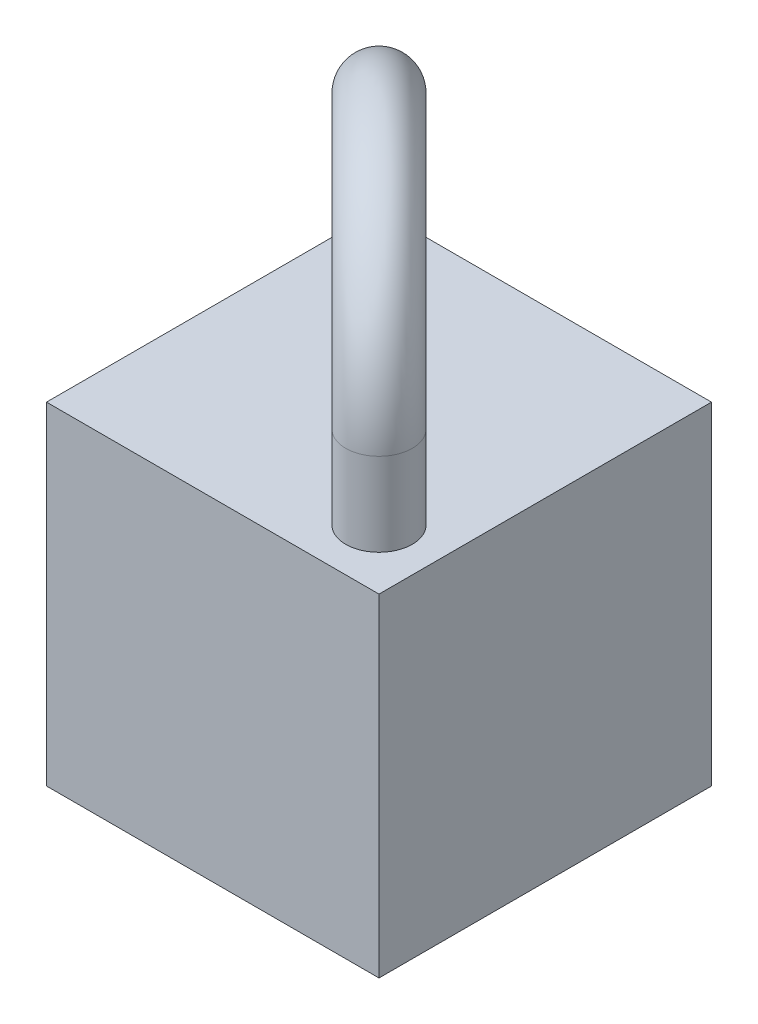
SolidWorks part; units mm, degrees
ref_plane "Front Plane" through (0, 0, 0) normal (0, 0, 1) x (1, 0, 0)
ref_plane "Top Plane" through (0, 0, 0) normal (0, 1, 0) x (1, 0, 0)
ref_plane "Right Plane" through (0, 0, 0) normal (1, 0, 0) x (0, 0, -1)
sketch "Sketch1" plane through (0, 0, 0) normal (0, 1, 0) x (1, 0, 0)
  line L1 (-12.7, -12.7) -> (12.7, -12.7)
  line L2 (-12.7, -12.7) -> (-12.7, 12.7)
  line L3 (-12.7, 12.7) -> (12.7, 12.7)
  line L4 (12.7, -12.7) -> (12.7, 12.7)
  line L5 (-12.7, -12.7) -> (12.7, 12.7) construction
  line L6 (-12.7, 12.7) -> (12.7, -12.7) construction
  point P0 (0, 0)
  dimension "D1" = 25.4
extrude "Boss-Extrude1" add sketch "Sketch1" along normal mid plane 25.4
ref_plane "Plane1" through (0, 19.05, 0) normal (0, 1, 0) x (1, 0, 0)
sketch "Sketch2" plane through (0, 19.05, 0) normal (0, 1, 0) x (1, 0, 0)
  line L0 (0, 0) -> (12.7, -12.7) construction
  line L1 (0, 0) -> (3.1076, 3.1076) construction
  circle A0 centre (8.1411, -8.1411) radius 2.54
  circle A1 centre (-8.1411, 8.1411) radius 2.54
  dimension "D1" = 5.08
revolve "Revolve1" add sketch "Sketch2" angle 180 about L1 region at (8.1411, 19.05, 8.1411) reverse direction yes
extrude "Boss-Extrude2" add sketch "Sketch2<3>" against normal up to body separate body
sketch "Sketch2<3>" plane through (0, 19.05, 0) normal (0, 1, 0) x (1, 0, 0) same geometry as "Sketch2"
